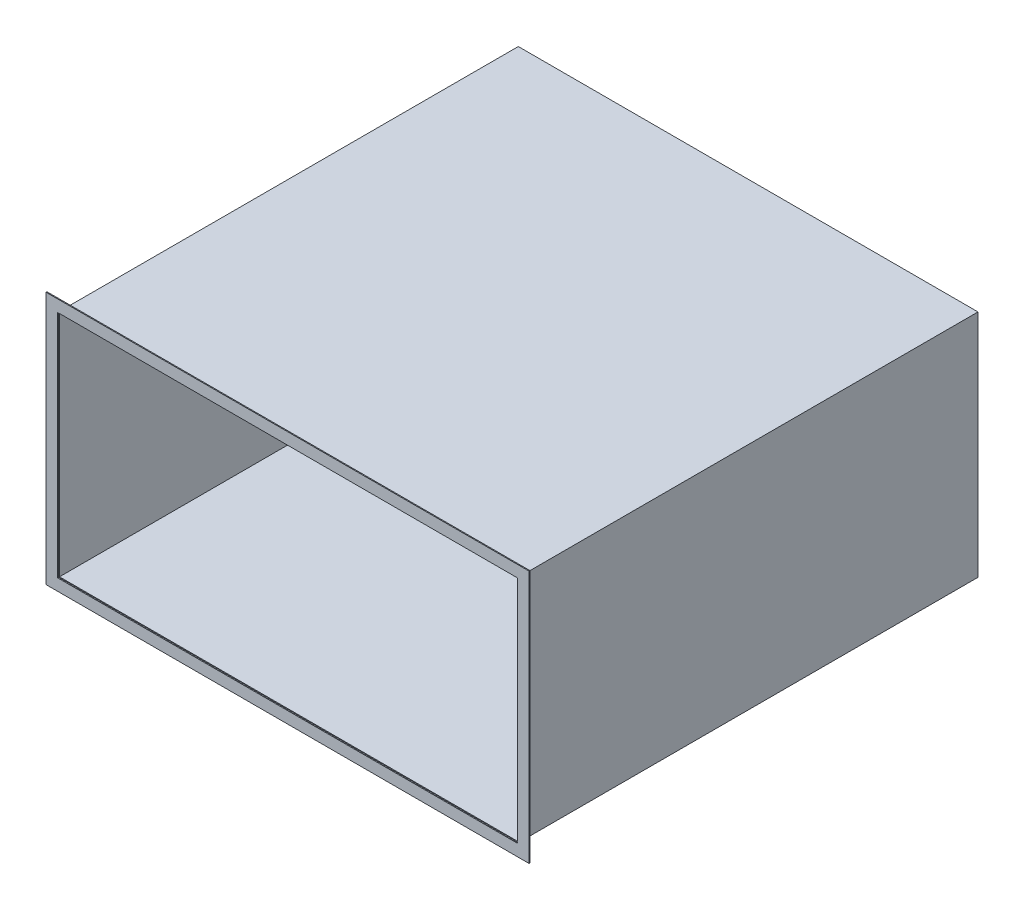
SolidWorks part; units mm, degrees
material "Plain Carbon Steel"
ref_plane "Front Plane" through (0, 0, 0) normal (0, 0, 1) x (1, 0, 0)
ref_plane "Top Plane" through (0, 0, 0) normal (0, 1, 0) x (1, 0, 0)
ref_plane "Right Plane" through (0, 0, 0) normal (1, 0, 0) x (0, 0, -1)
sketch "Sketch1" plane through (0, 0, 0) normal (0, 0, 1) x (1, 0, 0)
  line L1 (-500, 250) -> (500, 250)
  line L2 (-500, 250) -> (-500, -250)
  line L3 (-500, -250) -> (500, -250)
  line L4 (500, 250) -> (500, -250)
  line L5 (-500, 250) -> (500, -250) construction
  line L6 (-500, -250) -> (500, 250) construction
  point P0 (0, 0)
  dimension "Height" = 500
  dimension "Width" = 1000
extrude "Extrude" add sketch "Sketch1" along normal blind 1000 thin thin type one direction reverse wall 2
sketch "Sketch2" plane through (0, 0, 1000) normal (0, 0, 1) x (1, 0, 0)
  line L8 (525.4, -275.4) -> (525.4, 275.4)
  line L9 (525.4, 275.4) -> (-525.4, 275.4)
  line L10 (-525.4, 275.4) -> (-525.4, -275.4)
  line L11 (-525.4, -275.4) -> (525.4, -275.4)
  line L12 (525.4, -275.4) -> (525.4, 275.4)
  line L13 (525.4, 275.4) -> (-525.4, 275.4)
  line L14 (-525.4, 275.4) -> (-525.4, -275.4)
  line L15 (-525.4, -275.4) -> (525.4, -275.4)
  line L16 (500, -250) -> (500, 250)
  line L17 (500, 250) -> (-500, 250)
  line L18 (-500, 250) -> (-500, -250)
  line L19 (-500, -250) -> (500, -250)
  line L20 (500, -250) -> (500, 250)
  line L21 (500, 250) -> (-500, 250)
  line L22 (-500, 250) -> (-500, -250)
  line L23 (-500, -250) -> (500, -250)
  dimension "D1" = 25.4
  dimension "D2" = 0
extrude "Boss-Extrude1" add sketch "Sketch2" along normal blind 2 separate body
other "CPoint1" parameters "Diameter"=1954.41, "StubLength"=500
ref_axis "Axis1" through (0, 0, -10) along (0, 0, 1)
